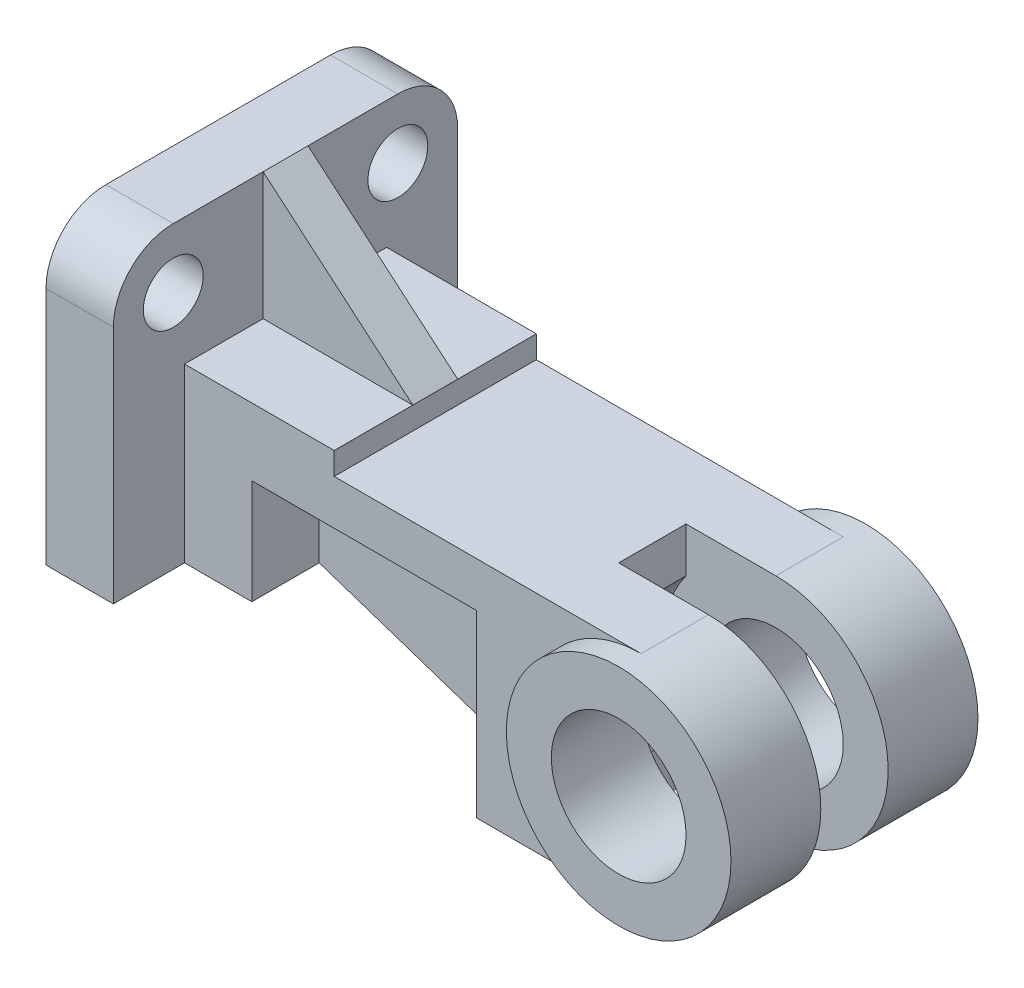
SolidWorks part; units mm, degrees
ref_plane "Front Plane" through (0, 0, 0) normal (0, 0, 1) x (1, 0, 0)
ref_plane "Top Plane" through (0, 0, 0) normal (0, 1, 0) x (1, 0, 0)
ref_plane "Right Plane" through (0, 0, 0) normal (1, 0, 0) x (0, 0, -1)
sketch "Sketch1" plane through (0, 0, 0) normal (0, 0, 1) x (1, 0, 0)
  line L0 (0, 0) -> (-28022.4027, 0) construction
  line L1 (0, 0) -> (0, -28022.4027) construction
  line L2 (0, 30) -> (-82, 30)
  line L3 (-104, -10) -> (-122, -10)
  line L4 (-122, 70) -> (-82, 36)
  line L5 (-140, 70) -> (-122, 70)
  line L6 (-122, 70) -> (-122, -10)
  line L7 (-122, -10) -> (-140, -10)
  line L8 (-140, -10) -> (-140, 70)
  line L9 (0, -30) -> (-44, -30)
  line L10 (-44, -30) -> (-104, -10)
  line L11 (-82, 36) -> (-82, 30)
  line L12 (-82, 36) -> (-122, 36)
  line L13 (-104, -10) -> (-104, 18)
  line L14 (-104, 18) -> (-44, 18)
  line L15 (-44, 18) -> (-44, -30)
  circle A0 centre (0, 0) radius 18
  circle A1 centre (0, 0) radius 30
  dimension "D1" = 60
  dimension "D2" = 36
  dimension "D3" = 44
  dimension "D4" = 60
  dimension "D5" = 140
  dimension "D6" = 18
  dimension "D7" = 40
  dimension "D8" = 6
  dimension "D9" = 80
  dimension "D10" = 40
  dimension "D11" = 12
extrude "Boss-Extrude1" add sketch "Sketch1" along normal mid plane 92 contours L8 L7 L6 L5 region at (-131, 30, 0)
extrude "Boss-Extrude2" add sketch "Sketch1<3>" along normal mid plane 54 contours A1 L2 L11 L12 L6 L3 L13 L14 L15 L9 region at (-31.3871, 0, 0)
sketch "Sketch1<3>" plane through (0, 0, 0) normal (0, 0, 1) x (1, 0, 0) same geometry as "Sketch1"
extrude "Boss-Extrude3" add sketch "Sketch1<4>" along normal blind 24 from offset 9 contours A1 A0 region at (20.6132, 20.6132, 0)
sketch "Sketch1<4>" plane through (0, 0, 0) normal (0, 0, 1) x (1, 0, 0) same geometry as "Sketch1"
mirror "Mirror1" about plane through (0, 0, 0) normal (0, 0, 1) of "Boss-Extrude3"
fillet "Fillet1" radius 16 2 edges at (-131, 70, -46) (-131, 70, 46)
extrude "Boss-Extrude4" add sketch "Sketch1<7>" along normal mid plane 12 contours L12 L4 L6 region at (-108.6667, 47.3333, 0)
sketch "Sketch1<7>" plane through (0, 0, 0) normal (0, 0, 1) x (1, 0, 0) same geometry as "Sketch1"
extrude "Boss-Extrude5" add sketch "Sketch1<8>" along normal mid plane 18 contours L15 L14 L13 L10 region at (-71.3684, -1.4386, 0)
sketch "Sketch1<8>" plane through (0, 0, 0) normal (0, 0, 1) x (1, 0, 0) same geometry as "Sketch1"
hole_wizard "Ø16.0mm Dowel Hole1" positions "3DSketch1" profile "Sketch2" hole size "Ø16.0" standard "ANSI Metric" end condition through all
sketch3d "3DSketch1"
  line L0 (-140, 54, 30) -> (-122, 54, 30) construction
  line L1 (-122, 54, -30) -> (-140, 54, -30) construction
  point P0 (-122, 54, 30)
  point P4 (-122, 54, -30)
sketch "Sketch2" plane through (-122, 54, 30) normal (0, 1, 0) x (0, 0, -1)
  line L0 (0, 0) -> (0, 18)
  line L1 (0, 18) -> (8, 18)
  line L2 (8, 18) -> (8, 0)
  line L5 (8, 0) -> (0, 0)
  line L11 (0, -6.35) -> (0, 107.95) construction
  dimension "Thru Hole Dia." = 16
  dimension "Thru Hole Depth" = 18
sketch "Sketch3" plane through (0, 30, 0) normal (0, 1, 0) x (1, 0, 0)
  line L1 (24, 9) -> (-24, 9)
  line L2 (24, 9) -> (24, -9)
  line L3 (24, -9) -> (-24, -9)
  line L4 (-24, 9) -> (-24, -9)
  line L5 (0, -9) -> (0, 9) construction
  line L6 (24, 0) -> (-24, 0) construction
  point P0 (0, 0)
  dimension "D1" = 48
  dimension "D2" = 18
extrude "Cut-Extrude1" cut sketch "Sketch3" against normal blind 88
